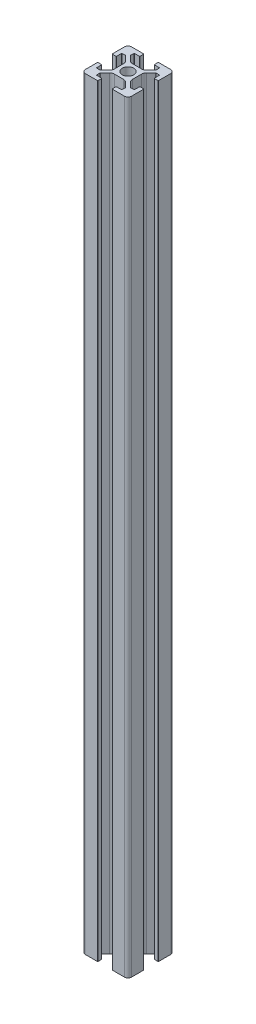
SolidWorks part; units mm, degrees
ref_plane "Front Plane" through (0, 0, 0) normal (0, 0, 1) x (1, 0, 0)
ref_plane "Top Plane" through (0, 0, 0) normal (0, 1, 0) x (1, 0, 0)
ref_plane "Right Plane" through (0, 0, 0) normal (1, 0, 0) x (0, 0, -1)
sketch "Sketch1" plane through (0, 0, 0) normal (0, 1, 0) x (1, 0, 0)
  line L0 (10, 20) -> (10, 10) construction
  line L1 (0, 0) -> (20, 0)
  line L2 (0, 0) -> (0, 20)
  line L3 (0, 20) -> (20, 20)
  line L4 (20, 0) -> (20, 20)
  line L5 (6.1, 13.9) -> (13.9, 13.9)
  line L6 (6.1, 13.9) -> (6.1, 6.1)
  line L7 (6.1, 6.1) -> (13.9, 6.1)
  line L8 (13.9, 13.9) -> (13.9, 6.1)
  line L9 (10, 10) -> (0, 10) construction
  line L10 (2.8607, 18.2) -> (18.2, 2.8607)
  line L11 (1.8, 18.2) -> (18.2, 18.2)
  line L12 (1.8, 18.2) -> (1.8, 1.8)
  line L13 (1.8, 1.8) -> (18.2, 1.8)
  line L14 (18.2, 18.2) -> (18.2, 1.8)
  line L15 (1.8, 17.1393) -> (17.1393, 1.8)
  line L16 (17.1393, 18.2) -> (1.8, 2.8607)
  line L17 (18.2, 17.1393) -> (2.8607, 1.8)
  line L18 (1.8, 18.2) -> (18.2, 1.8) construction
  line L19 (1.8, 17.1393) -> (2.3303, 17.6697) construction
  line L20 (2.3303, 17.6697) -> (2.8607, 18.2) construction
  line L21 (1.8, 1.8) -> (18.2, 18.2) construction
  line L22 (18.2, 1.8) -> (15.5, 1.8)
  line L23 (18.2, 1.8) -> (18.2, 4.5)
  line L24 (18.2, 4.5) -> (15.5, 4.5)
  line L25 (15.5, 1.8) -> (15.5, 4.5)
  line L26 (18.2, 13.1) -> (20, 13.1)
  line L27 (18.2, 18.2) -> (15.5, 18.2)
  line L28 (18.2, 18.2) -> (18.2, 15.5)
  line L29 (18.2, 15.5) -> (15.5, 15.5)
  line L30 (15.5, 18.2) -> (15.5, 15.5)
  line L31 (18.2, 6.9) -> (20, 6.9)
  line L32 (4.5, 18.2) -> (4.5, 15.5)
  line L33 (1.8, 15.5) -> (4.5, 15.5)
  line L34 (4.5, 1.8) -> (4.5, 4.5)
  line L35 (1.8, 4.5) -> (4.5, 4.5)
  line L36 (1.8, 6.9) -> (0, 6.9)
  line L37 (1.8, 13.1) -> (0, 13.1)
  line L38 (6.9, 20) -> (6.9, 18.2)
  line L39 (13.1, 20) -> (13.1, 18.2)
  line L40 (6.9, 0) -> (6.9, 1.8)
  line L41 (13.1, 0) -> (13.1, 1.8)
  circle A0 centre (10, 10) radius 2.5
  point P9 (10, 20)
  point P10 (10, 13.9)
  point P11 (0, 10)
  point P12 (6.1, 10)
  point P21 (10, 18.2)
  point P22 (1.8, 10)
  dimension "D3" = 5
  dimension "D1" = 20
  dimension "D2" = 6.1
  dimension "D4" = 1.5
  dimension "D5" = 1.5
  dimension "D6" = 1.8
  dimension "D7" = 11
  dimension "D8" = 6.2
  dimension "D9" = 6.9
  dimension "D10" = 6.2
  dimension "D11" = 6.9
extrude "Boss-Extrude1" add sketch "Sketch1" along normal blind 330 contours L38 L3 L2 L37 L12 L11 | L15 L33 L32 L10 L11 L12 | L32 L11 L10 | L12 L33 L15 | L33 L15 L6 L5 L10 L32 | L3 L39 L11 L14 L26 L4 | L11 L30 L16 | L16 L30 L29 L17 L14 L11 | L29 L14 L17 | L30 L16 L5 L8 L17 L29 | A0 L16 L5 L10 | A0 L10 L5 L6 L15 | A0 L17 L8 L5 L16 | A0 L10 L8 L17 | A0 L15 L6 L16 | A0 L16 L6 L7 L17 | A0 L17 L7 L15 | A0 L15 L7 L8 L10 | L16 L35 L34 L17 L7 L6 | L15 L25 L24 L10 L8 L7 | L35 L12 L16 | L35 L16 L12 L13 L17 L34 | L13 L34 L17 | L1 L40 L13 L12 L36 L2 | L14 L24 L10 | L25 L15 L13 L14 L10 L24 | L25 L13 L15 | L41 L1 L4 L31 L14 L13 region at (0.0976, 0, -3.45) region at (13.1976, 0, -0.9) region at (0.0976, 0, -16.55) region at (3.9536, 0, -2.3464) region at (2.3464, 0, -3.9536) region at (16.0464, 0, -2.3464) region at (3.15, 0, -3.15) region at (5.3, 0, -5.3) region at (2.3464, 0, -16.0464) region at (19.1, 0, -13.1976) region at (16.85, 0, -3.15) region at (14.7, 0, -5.3) region at (10, 0, -6.764) region at (7.3061, 0, -7.3061) region at (3.15, 0, -16.85) region at (5.3, 0, -14.7) region at (6.764, 0, -10) region at (17.6536, 0, -3.9536) region at (12.6939, 0, -7.3061) region at (3.9536, 0, -17.6536) region at (7.3061, 0, -12.6939) region at (17.6536, 0, -16.0464) region at (16.0464, 0, -17.6536) region at (16.85, 0, -16.85) region at (14.7, 0, -14.7) region at (13.236, 0, -10) region at (10, 0, -13.236) region at (12.6939, 0, -12.6939)
fillet "Fillet1" radius 1.5 4 edges at (0, 165, -20) (0, 165, 0) (20, 165, -20) (20, 165, 0)
fillet "Fillet2" radius 0.2 32 edges at (20, 165, -13.1) (6.9, 165, -18.2) (0, 165, -13.1) (13.1, 165, -18.2) (18.2, 165, -13.1) (13.1, 165, 0) (13.1, 165, -1.8) (6.9, 165, 0) (6.9, 165, -1.8) (0, 165, -6.9) (1.8, 165, -6.9) (1.8, 165, -13.1) (6.9, 165, -20) (13.1, 165, -20) (18.2, 165, -6.9) (20, 165, -6.9) (4.5, 165, -3.4393) (15.5, 165, -3.4393) (18.2, 165, -4.5) (16.5607, 165, -4.5) (18.2, 165, -15.5) (16.5607, 165, -15.5) (15.5, 165, -16.5607) (15.5, 165, -18.2) (4.5, 165, -16.5607) (4.5, 165, -18.2) (3.4393, 165, -15.5) (1.8, 165, -15.5) (3.4393, 165, -4.5) (1.8, 165, -4.5) (15.5, 165, -1.8) (4.5, 165, -1.8)
fillet "Fillet3" radius 2 8 edges at (13.9, 165, -7.1607) (12.8393, 165, -6.1) (7.1607, 165, -6.1) (6.1, 165, -12.8393) (6.1, 165, -7.1607) (12.8393, 165, -13.9) (7.1607, 165, -13.9) (13.9, 165, -12.8393)
sketch "Sketch2" plane through (0, 0, -20) normal (0, 0, -1) x (-1, 0, 0)
  line L0 (-10, 330) -> (-10, 0) construction
  line L1 (-7.9891, 330) -> (-12.0109, 330) construction
  line L2 (-7.9891, 0) -> (-12.0109, 0) construction
  circle A0 centre (-10, 297) radius 2.1
  circle A1 centre (-10, 254) radius 2.1
  circle A2 centre (-10, 53) radius 2.1
  circle A3 centre (-10, 10) radius 2.1
  dimension "D3" = 4.2
  dimension "D1" = 43
  dimension "D2" = 33
  dimension "D4" = 10
  dimension "D5" = 43
extrude "Cut-Extrude1" cut sketch "Sketch2" against normal through all
